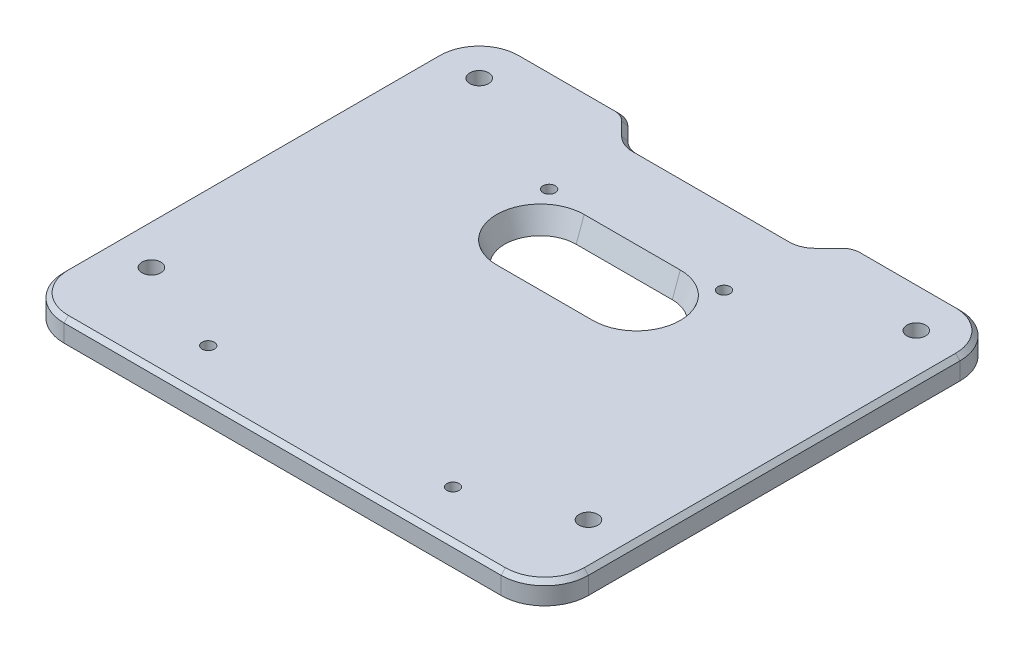
SolidWorks part; units mm, degrees
ref_plane "Front Plane" through (0, 0, 0) normal (0, 0, 1) x (1, 0, 0)
ref_plane "Top Plane" through (0, 0, 0) normal (0, 1, 0) x (1, 0, 0)
ref_plane "Right Plane" through (0, 0, 0) normal (1, 0, 0) x (0, 0, -1)
sketch "Sketch1" plane through (0, 0, 0) normal (0, 1, 0) x (1, 0, 0)
  line L0 (0, 0) -> (0, -28) construction
  line L1 (0, -28) -> (-28, -28) construction
  line L2 (0, -28) -> (28, -28) construction
  line L3 (0, 0) -> (0, 42) construction
  line L4 (0, 42) -> (20, 42) construction
  line L5 (0, 42) -> (-20, 42) construction
  line L6 (-15, -36.5) -> (15, -36.5) construction
  line L7 (-15, -34.85) -> (15, -34.85)
  line L8 (-15, -38.15) -> (15, -38.15)
  line L9 (0, 0) -> (0, -36.5) construction
  circle A0 centre (0, 0) radius 35 construction
  circle A1 centre (28, -28) radius 1.4
  circle A2 centre (-28, -28) radius 1.4
  circle A3 centre (-20, 42) radius 1.4
  circle A4 centre (20, 42) radius 1.4
  arc A5 (-15, -34.85) -> (-15, -38.15) centre (-15, -36.5) ccw
  arc A6 (15, -38.15) -> (15, -34.85) centre (15, -36.5) ccw
  point P15 (0, -36.5)
  dimension "D1" = 70
  dimension "D6" = 2.8
  dimension "D9" = 1.65
  dimension "D2" = 28
  dimension "D3" = 42
  dimension "D4" = 56
  dimension "D5" = 40
  dimension "D7" = 30
  dimension "D8" = 36.5
sketch "Sketch2" plane through (0, 0, 0) normal (0, 1, 0) x (1, 0, 0)
  line L0 (0, 0) -> (0, 66) construction
  line L1 (-60, 66) -> (60, 66)
  line L2 (-60, 66) -> (-60, -39)
  line L4 (60, 66) -> (60, -39)
  line L6 (-60, -39) -> (60, -39)
  circle A0 centre (-28, -28) radius 1.4 construction
  circle A1 centre (28, -28) radius 1.4 construction
  circle A2 centre (20, 42) radius 1.4 construction
  circle A3 centre (-20, 42) radius 1.4 construction
  circle A4 centre (-28, -28) radius 1.4
  circle A5 centre (28, -28) radius 1.4
  circle A6 centre (20, 42) radius 1.4
  circle A7 centre (-20, 42) radius 1.4
  dimension "D1" = 120
  dimension "D2" = 105
  dimension "D3" = 66
extrude "Boss-Extrude2" add sketch "Sketch2" along normal blind 5
sketch "Sketch9" plane through (0, 5, 0) normal (0, 1, 0) x (1, 0, 0)
  line L0 (-26, 66) -> (-20, 60)
  line L7 (60, 66) -> (-60, 66) construction
  line L8 (-20, 60) -> (20, 60)
  line L9 (20, 60) -> (26, 66)
  line L10 (26, 66) -> (-26, 66)
  line L11 (0, 66) -> (0, 60) construction
  line L12 (0, 60) -> (0, 0) construction
  point P10 (18.697, 60.1714)
  dimension "D1" = 6
  dimension "D2" = 45
  dimension "D3" = 40
extrude "Cut-Extrude13" cut sketch "Sketch9" against normal through all
fillet "Fillet6" radius 5 4 edges at (26, 2.5, -66) (20, 2.5, -60) (-26, 2.5, -66) (-20, 2.5, -60)
fillet "Fillet5" radius 10 4 edges at (-60, 2.5, -66) (60, 2.5, -66) (60, 2.5, 39) (-60, 2.5, 39)
chamfer "Chamfer4" distance 1 angle 45 15 edges at (-57.0711, 5, 36.0711) (-60, 5, -13.5) (-57.0711, 5, -63.0711) (0, 5, 39) (57.0711, 5, 36.0711) (57.0711, 5, -63.0711) (60, 5, -13.5) (-39.0355, 5, -66) (-23, 5, -63) (-26.1577, 5, -65.6194) (-19.8423, 5, -60.3806) (0, 5, -60) (19.8423, 5, -60.3806) (23, 5, -63) (26.1577, 5, -65.6194)
sketch "Sketch11" plane through (0, 5, 0) normal (0, 1, 0) x (1, 0, 0)
  line L0 (0, 0) -> (0, 42) construction
  line L1 (50, -19) -> (-50, -19) construction
  line L2 (50, -19) -> (50, 56) construction
  line L3 (50, 56) -> (-50, 56) construction
  line L4 (-50, -19) -> (-50, 56) construction
  line L5 (50, -19) -> (-50, 56) construction
  line L6 (50, 56) -> (-50, -19) construction
  circle A0 centre (-50, 56) radius 2.15
  circle A1 centre (50, 56) radius 2.15
  circle A2 centre (-50, -19) radius 2.15
  circle A3 centre (50, -19) radius 2.15
  point P0 (0, 18.5)
  dimension "D4" = 4.3
  dimension "D1" = 100
  dimension "D2" = 56
  dimension "D3" = 75
extrude "Cut-Extrude10" cut sketch "Sketch11" against normal through all
sketch "Sketch13" plane through (0, 0, 0) normal (0, -1, 0) x (1, 0, 0)
  circle A0 centre (-28, 28) radius 3.25
  circle A1 centre (28, 28) radius 3.25
  circle A2 centre (-20, -42) radius 3.25
  circle A3 centre (20, -42) radius 3.25
  dimension "D1" = 6.5
extrude "Cut-Extrude12" cut sketch "Sketch13" against normal blind 2.5
sketch "Sketch14" plane through (0, 5, 0) normal (0, 1, 0) x (1, 0, 0)
  line L0 (0, 0) -> (0, 31) construction
  line L1 (-11, 31) -> (11, 31) construction
  line L2 (-11, 38) -> (11, 38)
  line L3 (-11, 24) -> (11, 24)
  arc A0 (-11, 38) -> (-11, 24) centre (-11, 31) ccw
  arc A1 (11, 24) -> (11, 38) centre (11, 31) ccw
  point P5 (9.9812, 38.1027)
  point P10 (0, 31.233)
  dimension "D3" = 7
  dimension "D1" = 31
  dimension "D2" = 22
extrude "Cut-Extrude14" cut sketch "Sketch14" against normal through all
chamfer "Chamfer5" distance 3 angle 70 4 edges at (0, 5, -24) (18, 5, -31) (-18, 5, -31) (0, 5, -38) first distance on face at (0, 5, -31)
